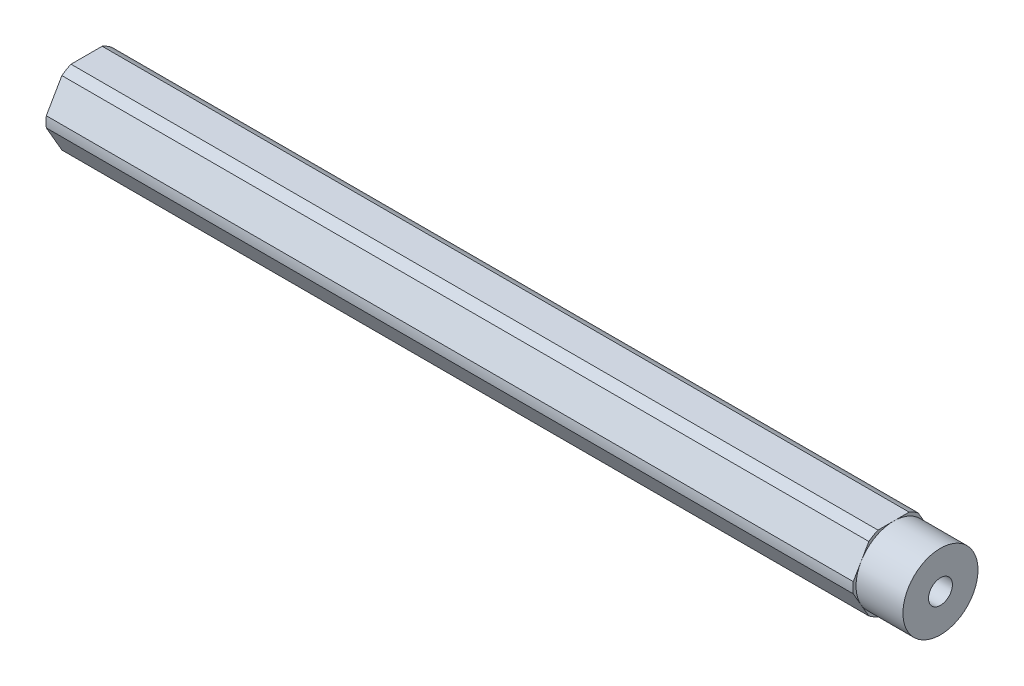
SolidWorks part; units mm, degrees
material "7075-T6 (SN)"
ref_plane "Front Plane" through (0, 0, 0) normal (0, 0, 1) x (1, 0, 0)
ref_plane "Top Plane" through (0, 0, 0) normal (0, 1, 0) x (1, 0, 0)
ref_plane "Right Plane" through (0, 0, 0) normal (1, 0, 0) x (0, 0, -1)
sketch "Sketch1" plane through (0, 0, 0) normal (1, 0, 0) x (0, 0, -1)
  line L1 (3.6662, 6.35) -> (-3.6662, 6.35)
  line L2 (-3.6662, 6.35) -> (-7.3323, 0)
  line L3 (-7.3323, 0) -> (-3.6662, -6.35)
  line L4 (-3.6662, -6.35) -> (3.6662, -6.35)
  line L5 (3.6662, -6.35) -> (7.3323, 0)
  line L6 (7.3323, 0) -> (3.6662, 6.35)
  circle A0 centre (0, 0) radius 6.875
  circle A1 centre (0, 0) radius 2.0193
  circle A2 centre (0, 0) radius 6.35 construction
  dimension "D1" = 12.7
  dimension "D2" = 13.75
  dimension "D3" = 4.0386
extrude "Boss-Extrude1" add sketch "Sketch1" along normal mid plane 144.4625 contours L6 A0 L1 L2 L3 L4 L5 A1 region at (0, 5.7918, -3.3439)
hole_wizard "#10-32 Tapped Hole1" positions "3DSketch1" profile "Sketch2" tap size "#10-32" standard "ANSI Inch"
sketch3d "3DSketch1"
  circle A0 centre (-72.2313, 0, 0) radius 2.0193 construction
  circle A1 centre (72.2313, 0, 0) radius 2.0193 construction
  point P0 (72.2313, 0, 0)
  point P2 (-72.2313, 0, 0)
  point P7 (-70.212, 0, 0)
  point P10 (74.2506, 0, 0)
sketch "Sketch2" plane through (72.2313, 0, 0) normal (0, 1, 0) x (0, 0, -1)
  line L0 (0, 0) -> (0, 17.5608)
  line L1 (0, 17.5608) -> (2.0193, 16.3474)
  line L2 (2.0193, 16.3474) -> (2.0193, 0)
  line L5 (2.0193, 0) -> (0, 0)
  line L10 (0, 17.5608) -> (-2.0193, 16.3474) construction
  line L11 (0, -6.35) -> (0, 107.95) construction
  dimension "Tap Drill Dia." = 4.0386
  dimension "Tap Drill Depth" = 16.3474
  dimension "Drill Angle" = 118
cosmetic thread "Hole Thread1" parameters "D1"=13.97, "D2"=4.826
cosmetic thread "Hole Thread2" parameters "D1"=13.97, "D2"=4.826
sketch "Sketch3" plane through (72.2313, 0, 0) normal (1, 0, 0) x (0, 0, -1)
  circle A0 centre (0, 0) radius 6.35
  dimension "D1" = 12.7
extrude "Cut-Extrude-Thin1" cut sketch "Sketch3" against normal blind 7.9375 thin thin type one direction wall 2.54
equation "\"D2@Sketch1\"=13.75mm"
